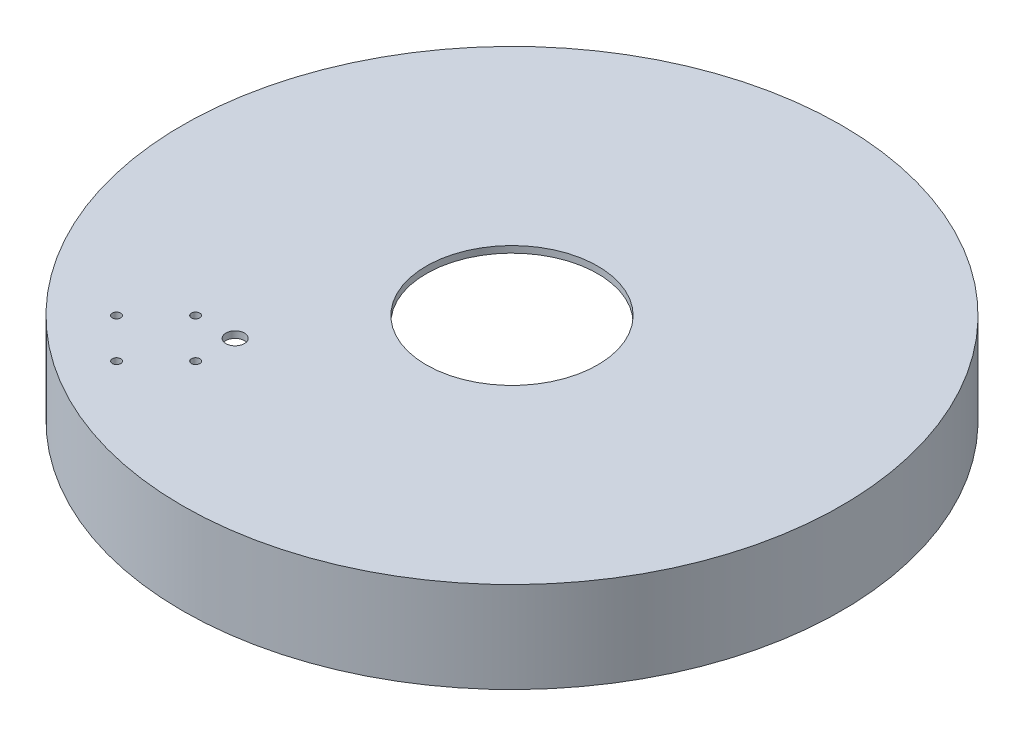
SolidWorks part; units mm, degrees
ref_plane "Front Plane" through (0, 0, 0) normal (0, 0, 1) x (1, 0, 0)
ref_plane "Top Plane" through (0, 0, 0) normal (0, 1, 0) x (1, 0, 0)
ref_plane "Right Plane" through (0, 0, 0) normal (1, 0, 0) x (0, 0, -1)
sketch "Sketch1" plane through (0, 0, 0) normal (0, 1, 0) x (1, 0, 0)
  circle A0 centre (0, 0) radius 125
  circle A1 centre (0, 0) radius 123
  dimension "D1" = 250
  dimension "D2" = 246
extrude "Boss-Extrude1" add sketch "Sketch1" along normal blind 32
sketch "Sketch2" plane through (0, 32, 0) normal (0, 1, 0) x (1, 0, 0)
  circle A0 centre (0, 0) radius 125
  circle A1 centre (0, 0) radius 32.5
  dimension "D1" = 65
extrude "Boss-Extrude2" add sketch "Sketch2" along normal blind 2.5
sketch "Sketch3" plane through (0, 34.5, 0) normal (0, 1, 0) x (1, 0, 0)
  circle A0 centre (-75, -75) radius 1.6
  circle A1 centre (-60, -60) radius 1.6
  circle A2 centre (-45, -75) radius 1.6
  circle A3 centre (-60, -90) radius 1.6
  point P8 (-63.4377, -68.7691)
  point P12 (-65.0449, -37.1698)
  dimension "D1" = 3.2
  dimension "D2" = 3.2
  dimension "D3" = 3.2
  dimension "D4" = 3.2
  dimension "D5" = 30
  dimension "D6" = 30
  dimension "D7" = 15
  dimension "D8" = 15
  dimension "D9" = 60
  dimension "D10" = 60
extrude "Cut-Extrude1" cut sketch "Sketch3" against normal up to surface (2.5 mm away) up to face at (0, 32, 32.5)
sketch "Sketch4" plane through (0, 34.5, 0) normal (0, 1, 0) x (1, 0, 0)
  circle A0 centre (-45, -60) radius 3.5
  circle A1 centre (-60, -60) radius 1.6 construction
  circle A2 centre (-45, -75) radius 1.6 construction
  dimension "D1" = 7
  dimension "D2" = 15
  dimension "D3" = 15
extrude "Cut-Extrude2" cut sketch "Sketch4" against normal up to surface (2.5 mm away) up to face at (-75, 32, 76.6)
